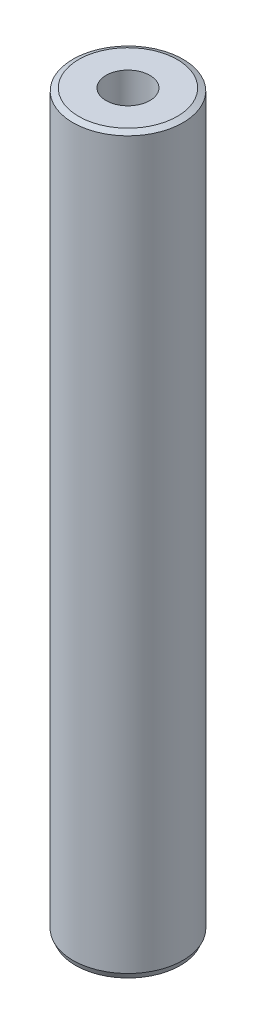
SolidWorks part; units mm, degrees
ref_plane "Front Plane" through (0, 0, 0) normal (0, 0, 1) x (1, 0, 0)
ref_plane "Top Plane" through (0, 0, 0) normal (0, 1, 0) x (1, 0, 0)
ref_plane "Right Plane" through (0, 0, 0) normal (1, 0, 0) x (0, 0, -1)
sketch "Sketch1" plane through (0, 0, 0) normal (0, 1, 0) x (1, 0, 0)
  circle A0 centre (0, 0) radius 45
  dimension "SHAFT_OD" = 90
extrude "Boss-Extrude1" add sketch "Sketch1" along normal blind 600
sketch "Sketch2" plane through (0, 0, 0) normal (0, 1, 0) x (1, 0, 0)
  circle A0 centre (0, 0) radius 17.9281
  dimension "BORE_D" = 35.8563
extrude "Cut-Extrude1" cut sketch "Sketch2" along normal through all
chamfer "Chamfer1" distance 2.105 angle 65.79 2 edges at (0, 600, 45) (0, 0, 45) first distance on face at (0, 600, 45) first distance on face at (0, 0, 17.9281)
